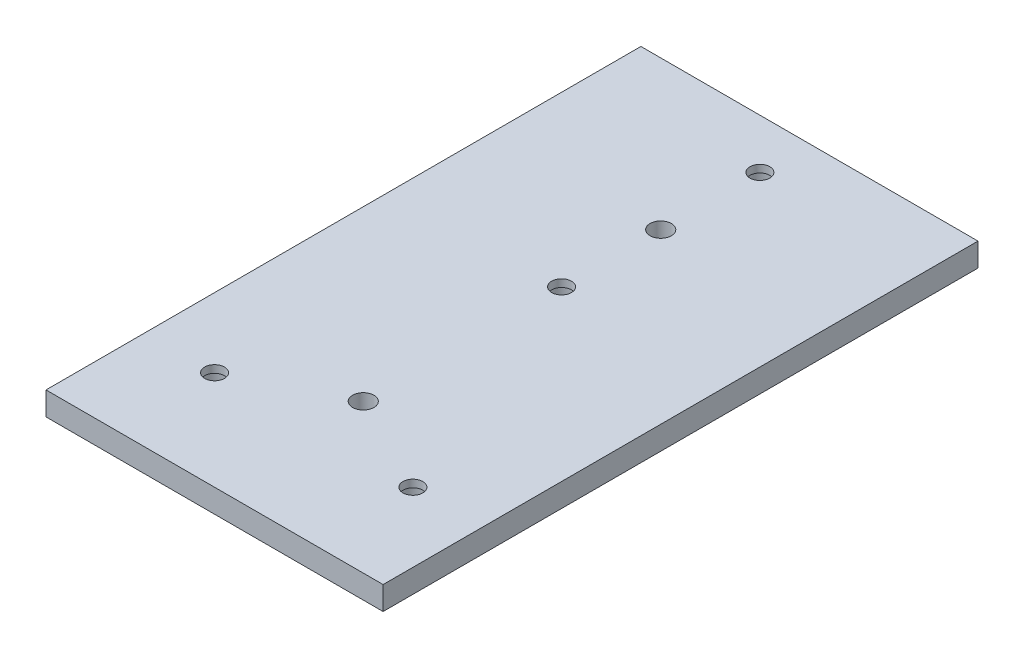
SolidWorks part; units mm, degrees
material "Melamine resin"
ref_plane "Front Plane" through (0, 0, 0) normal (0, 0, 1) x (1, 0, 0)
ref_plane "Top Plane" through (0, 0, 0) normal (0, 1, 0) x (1, 0, 0)
ref_plane "Right Plane" through (0, 0, 0) normal (1, 0, 0) x (0, 0, -1)
sketch "Sketch2" plane through (0, 0, 0) normal (0, 1, 0) x (1, 0, 0)
  line L1 (0, 0) -> (88.9, 0)
  line L2 (0, 0) -> (0, 152.4)
  line L3 (0, 152.4) -> (88.9, 152.4)
  line L10 (88.9, 152.4) -> (88.9, 0)
  dimension "D1" = 152.4
  dimension "D2" = 88.9
extrude "Boss-Extrude1" add sketch "Sketch2" along normal blind 5.9944 contours L3 L10 L1 L2
sketch "Sketch4" plane through (0, 5.9944, 0) normal (0, 1, 0) x (1, 0, 0)
  line L0 (0, 0) -> (0, 152.4) construction
  line L2 (45.72, 114.3) -> (45.72, 38.1) construction
  circle A0 centre (45.72, 114.3) radius 2.7305
  circle A1 centre (45.72, 38.1) radius 2.7305
  point P4 (0, 76.2)
  point P6 (45.72, 76.2)
  dimension "D3" = 5.461
  dimension "D4" = 5.461
  dimension "D1" = 76.2
  dimension "D2" = 45.72
extrude "Cut-Extrude2" cut sketch "Sketch4" against normal through all both
sketch "Sketch7" plane through (0, 5.9944, 0) normal (0, 1, 0) x (1, 0, 0)
  line L0 (0, 0) -> (16.256, 0) construction
  line L1 (0, 152.4) -> (2.54, 152.4)
  line L2 (0, 152.4) -> (0, 0)
  line L3 (0, 0) -> (2.54, 0)
  line L4 (2.54, 152.4) -> (2.54, 0)
  dimension "D1" = 2.54
extrude "Cut-Extrude3" cut sketch "Sketch7" against normal through all both
sketch "Sketch8" plane through (0, 5.9944, 0) normal (0, 1, 0) x (1, 0, 0)
  line L0 (45.72, 139.7) -> (45.72, 88.9) construction
  line L1 (20.32, 25.4) -> (71.12, 25.4) construction
  line L2 (2.54, 0) -> (88.9, 0) construction
  line L3 (2.54, 152.4) -> (88.9, 152.4) construction
  circle A0 centre (20.32, 25.4) radius 2.54
  circle A1 centre (71.12, 25.4) radius 2.54
  circle A2 centre (45.72, 88.9) radius 2.54
  circle A3 centre (45.72, 139.7) radius 2.54
  point P10 (45.72, 0)
  point P11 (45.72, 25.4)
  point P12 (39.4053, 134.8654)
  point P13 (44.4978, 139.7542)
  point P14 (0, 0)
  point P15 (45.3126, 136.9024)
  point P18 (45.72, 152.4)
  point P19 (45.72, 114.3)
  dimension "D1" = 5.08
  dimension "D2" = 5.08
  dimension "D3" = 5.08
  dimension "D4" = 5.08
  dimension "D5" = 50.8
  dimension "D6" = 50.8
  dimension "D7" = 25.4
  dimension "D8" = 12.7
extrude "Cut-Extrude4" cut sketch "Sketch8" against normal through all both and the other way through all
sketch "Sketch9" plane through (0, 0, 0) normal (0, -1, 0) x (1, 0, 0)
  circle A0 centre (20.32, -25.4) radius 3.683
  circle A1 centre (71.12, -25.4) radius 3.683
  circle A2 centre (45.72, -88.9) radius 3.683
  circle A3 centre (45.72, -139.7) radius 3.683
  dimension "D1" = 7.366
  dimension "D2" = 7.366
  dimension "D3" = 7.366
  dimension "D4" = 7.366
extrude "Cut-Extrude5" cut sketch "Sketch9" against normal blind 4.064
equation "\"threaded_insert_hole\"=0.1472"
equation "\"th\"=1.25249"
